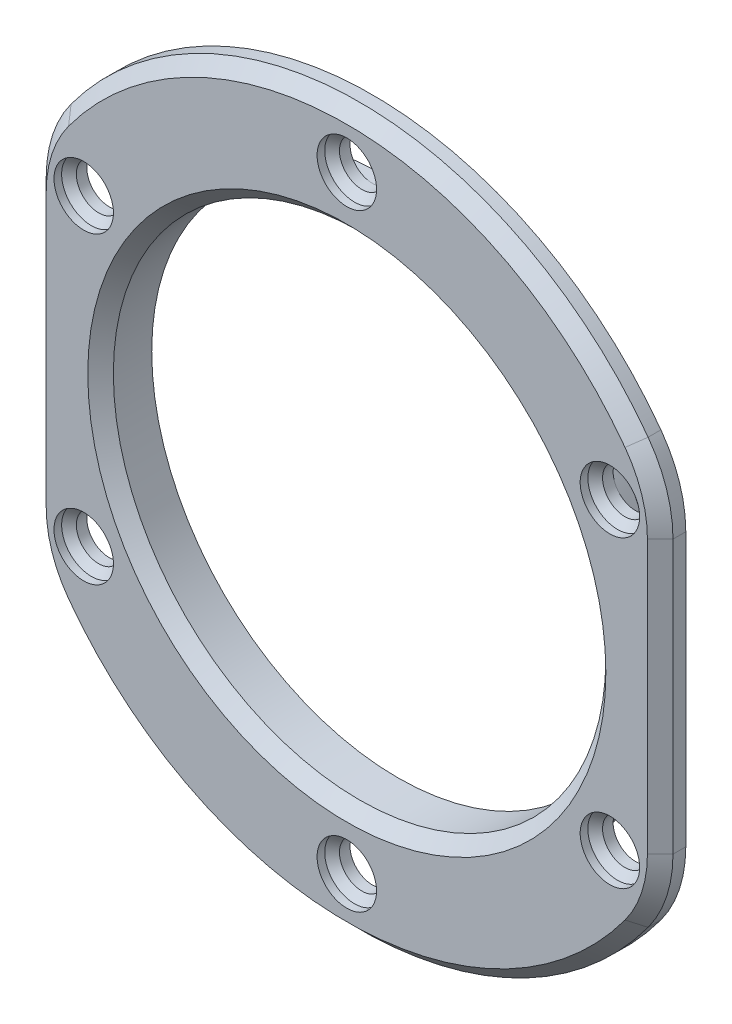
SolidWorks part; units mm, degrees
ref_plane "Front Plane" through (0, 0, 0) normal (0, 0, 1) x (1, 0, 0)
ref_plane "Top Plane" through (0, 0, 0) normal (0, 1, 0) x (1, 0, 0)
ref_plane "Right Plane" through (0, 0, 0) normal (1, 0, 0) x (0, 0, -1)
sketch "Sketch1" plane through (0, 0, 0) normal (0, 0, 1) x (1, 0, 0)
  circle A0 centre (0, 0) radius 19.25
  circle A1 centre (0, 0) radius 28
  dimension "D1" = 38.5
  dimension "D2" = 56
extrude "Boss-Extrude1" add sketch "Sketch1" along normal blind 2
sketch "Sketch2" plane through (0, 0, 0) normal (0, 0, -1) x (-1, 0, 0)
  circle A0 centre (0, 0) radius 19.25
  circle A1 centre (0, 0) radius 22
  circle A2 centre (0, 0) radius 19.25 construction
  dimension "D1" = 44
extrude "Boss-Extrude2" add sketch "Sketch2" along normal blind 2
sketch "Sketch3" plane through (0, 0, 2) normal (0, 0, 1) x (1, 0, 0)
  circle A0 centre (0, 23.75) radius 1.75
  circle A1 centre (20.5681, 11.875) radius 1.75
  circle A2 centre (20.5681, -11.875) radius 1.75
  circle A3 centre (0, -23.75) radius 1.75
  circle A4 centre (-20.5681, -11.875) radius 1.75
  circle A5 centre (-20.5681, 11.875) radius 1.75
  circle A6 centre (0, 0) radius 23.75 construction
  point P14 (0, 0)
  dimension "D2" = 3.5
  dimension "D3" = 47.5
  dimension "D1" = 6
extrude "Cut-Extrude1" cut sketch "Sketch3" against normal through all
sketch "Sketch4" plane through (0, 0, 2) normal (0, 0, 1) x (1, 0, 0)
  line L0 (0, 37.6944) -> (0, -37.3588) construction
  line L1 (24.5, 26.7836) -> (24.5, -27.4399)
  line L2 (-37.3946, 26.7836) -> (-24.5, 26.7836)
  line L3 (-37.3946, 26.7836) -> (-37.3946, -27.4399)
  line L4 (-37.3946, -27.4399) -> (-24.5, -27.4399)
  line L5 (-24.5, 26.7836) -> (-24.5, -27.4399)
  line L6 (37.3946, -27.4399) -> (24.5, -27.4399)
  line L7 (37.3946, 26.7836) -> (37.3946, -27.4399)
  line L8 (37.3946, 26.7836) -> (24.5, 26.7836)
  dimension "D1" = 49
extrude "Cut-Extrude2" cut sketch "Sketch4" against normal through all
fillet "Fillet1" radius 10 4 edges at (24.5, 13.5554, 1) (24.5, -13.5554, 1) (-24.5, -13.5554, 1) (-24.5, 13.5554, 1)
sketch "Sketch5" plane through (0, 0, 2) normal (0, 0, 1) x (1, 0, 0)
  circle A0 centre (0, 23.75) radius 2.325
  circle A1 centre (20.5681, 11.875) radius 2.325
  circle A2 centre (-20.5681, 11.875) radius 2.325
  circle A3 centre (20.5681, -11.875) radius 2.325
  circle A4 centre (0, -23.75) radius 2.325
  circle A5 centre (-20.5681, -11.875) radius 2.325
  dimension "D1" = 4.65
extrude "Cut-Extrude3" cut sketch "Sketch5" against normal blind 1.5
chamfer "Chamfer2" distance 0.9 angle 45 6 edges at (-18.2431, -11.875, 0.5) (2.325, -23.75, 0.5) (22.8931, -11.875, 0.5) (22.8931, 11.875, 0.5) (2.325, 23.75, 0.5) (-18.2431, 11.875, 0.5)
chamfer "Chamfer1" distance 1 angle 45 9 edges at (0, -28, 2) (24.0015, -13.7834, 2) (-24.0015, -13.7834, 2) (24.5, 0, 2) (-24.5, 0, 2) (24.0015, 13.7834, 2) (-24.0015, 13.7834, 2) (0, 28, 2) (19.25, 0, 2)
chamfer "Chamfer3" distance 1 angle 45 1 edges at (-22, 0, -2)
